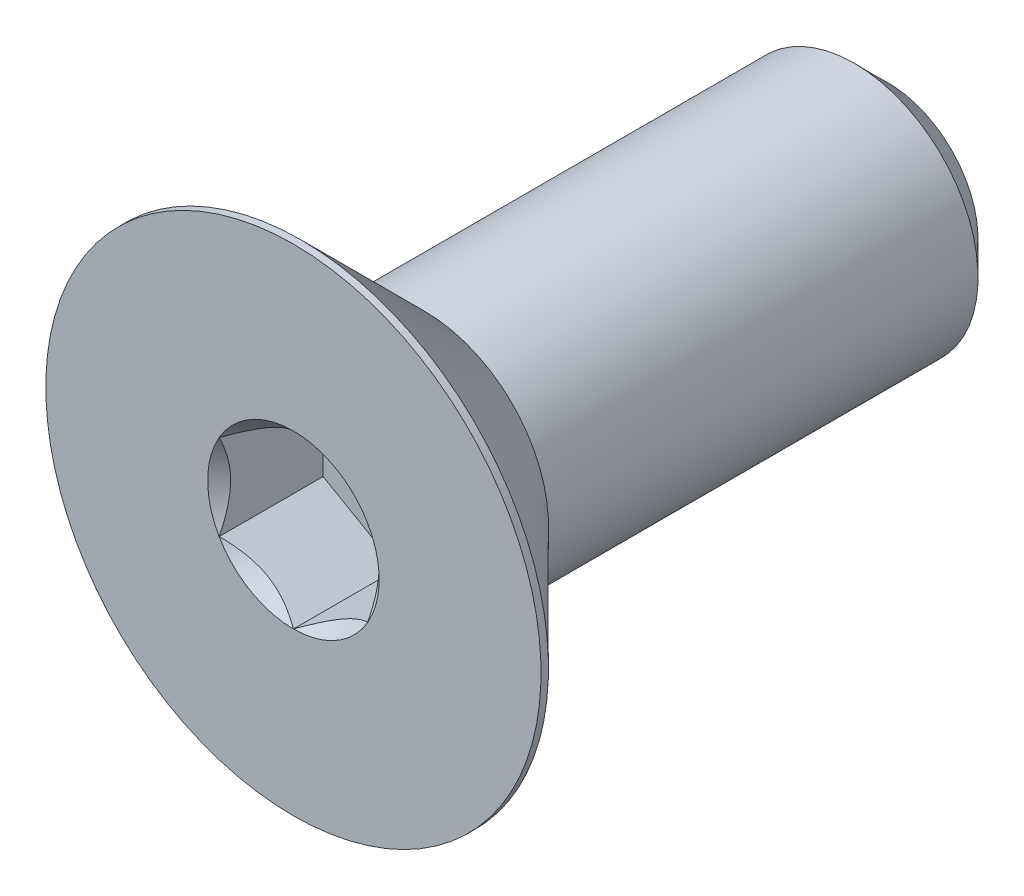
SolidWorks part; units mm, degrees
ref_plane "Front" through (0, 0, 0) normal (0, 0, 1) x (1, 0, 0)
ref_plane "Top" through (0, 0, 0) normal (0, 1, 0) x (1, 0, 0)
ref_plane "Right" through (0, 0, 0) normal (1, 0, 0) x (0, 0, -1)
sketch "Sketch11" plane through (0, 0, 0) normal (1, 0, 0) x (0, 0, -1)
  line L0 (-3, 2.5) -> (3, 2.5) construction
  line L5 (-3, 2.5) -> (-3, -2.5) construction
  line L6 (3, 1.25) -> (3, -1.25) construction
  line L7 (-2.99, 0.75) -> (-2.99, -0.75) construction
  line L8 (2.9719, 1.2987) -> (3.4219, 1.2987) construction
  line L9 (3.4219, 1.2987) -> (3.1969, 0.909) construction
  line L10 (3.1969, 0.909) -> (2.9719, 1.2987) construction
  line L11 (3.1688, 0.9577) -> (3.225, 0.9577) construction
  line L12 (3.1969, 0.9577) -> (3.1969, 0.909) construction
  line L13 (2.9859, 1.2744) -> (3.4078, 1.2744) construction
  line L14 (3.1969, 1.2987) -> (3.1969, 1.25) construction
  line L15 (3, 1.25) -> (3.3938, 1.25) construction
  line L17 (-2.925, 2.5) -> (-0.425, 0) construction
  line L18 (-0.425, 0) -> (-2.925, -2.5) construction
  point P3 (-1.5, 2.5)
  point P8 (0, 2.5)
  point P21 (3.1969, 1.2744)
  point P26 (-3, 0)
  point P28 (-2.99, 0)
  point P29 (3, 0)
  dimension "Length" = 6
  dimension "Head Diameter" = 5
  dimension "Thread Major Diameter" = 2.5
  dimension "Head Height" = 1.5
  dimension "Drive Size" = 1.5
  dimension "Thread Pitch" = 0.45
  dimension "D1" = 0.0563
  dimension "D2" = 0.01
  dimension "D3" = 0.075
  dimension "Countersink Angle" = 90
sketch "Sketch1" plane through (0, 0, 0) normal (1, 0, 0) x (0, 0, -1)
  line L2 (-1.5, 1.25) -> (3, 1.25)
  line L3 (3, 1.25) -> (3, 0)
  line L4 (-1.95, 1.25) -> (-1.95, 0)
  line L5 (-1.5, 1.25) -> (-1.95, 1.25)
  line L6 (-3, 2.5) -> (-3, -2.5) construction
  line L7 (3, 1.25) -> (3, -1.25) construction
  line L8 (-1.95, 0) -> (3, 0)
  dimension "D1" = 1.05
revolve "Revolve1" add sketch "Sketch1" angle 360 mid plane about L8
chamfer "Chamfer1" distance 0.3375 angle 45 1 edges at (0, -1.25, -3)
sketch "Sketch7" plane through (0, 0, 0) normal (1, 0, 0) x (0, 0, -1)
  line L2 (-3, 2.5) -> (-2.925, 2.5)
  line L5 (-1.5, 1.075) -> (-1.5, 0)
  line L6 (-3, 2.5) -> (-3, 0)
  line L8 (-3, 2.5) -> (-3, -2.5) construction
  line L9 (-3, 0) -> (-1.5, 0)
  line L12 (-2.925, 2.5) -> (-1.5, 1.075)
  line L13 (-2.925, 2.5) -> (-0.425, 0) construction
revolve "Revolve2" add sketch "Sketch7" angle 360 mid plane about L9 region at (0, 0.9623, 2.3521)
ref_plane "Plane1" through (0, 0, 1.5) normal (0, 0, 1) x (1, 0, 0)
sketch "Sketch5" plane through (0, 0, 3) normal (0, 0, 1) x (1, 0, 0)
  line L1 (0.75, -0.433) -> (0.75, 0.433)
  line L2 (0.75, 0.433) -> (0, 0.866)
  line L3 (0, 0.866) -> (-0.75, 0.433)
  line L4 (-0.75, 0.433) -> (-0.75, -0.433)
  line L5 (-0.75, -0.433) -> (0, -0.866)
  line L6 (0, -0.866) -> (0.75, -0.433)
  circle A0 centre (0, 0) radius 0.75 construction
extrude "Cut-Extrude2" cut sketch "Sketch5" against normal blind 1.05
sketch "Sketch6" plane through (0, 0, 3) normal (0, 0, -1) x (-1, 0, 0)
  circle A0 centre (0, 0) radius 0.866
extrude "Cut-Extrude3" cut sketch "Sketch6" along normal blind 1.05 draft 45
sketch "Sketch12" [suppressed] plane through (0, 0, -3) normal (0, 0, -1) x (-1, 0, 0)
  circle A0 centre (0, 0) radius 1.25 construction
  circle A1 centre (0, 0) radius 1.25
curve "Helix/Spiral1" [suppressed] pitch 0.45 height 6 turns 13.3333
sketch "Sketch13" [suppressed] plane through (0, 0, 0) normal (1, 0, 0) x (0, 0, -1)
  line L0 (2.9859, 1.2744) -> (3.4078, 1.2744)
  line L1 (3.4078, 1.2744) -> (3.225, 0.9577)
  line L2 (3.225, 0.9577) -> (3.1688, 0.9577)
  line L3 (3.1688, 0.9577) -> (2.9859, 1.2744)
sweep "Cut-Sweep1" [suppressed] cut profiles "Sketch13" path "Helix/Spiral1"
combine bodies "Combine1" [suppressed] operation type add bodies to combine 113 127
ref_axis "Axis1" through (0, 0, -3.3043) along (0, 0, 1)
equation "\"D1@Chamfer1\"=\"Thread Pitch@Sketch11\" * .75"
equation "\"D1@Cut-Extrude2\"= \"Head Height@Sketch11\" * .7"
equation "\"D1@Cut-Extrude3\" = \"D1@Cut-Extrude2\""
equation "\"D1@Sketch11\"=\"Thread Pitch@Sketch11\"/8"
equation "\"D3@Sketch11\"=\"Head Height@Sketch11\"*.05"
equation "\"D4@Helix/Spiral1\"=\"Thread Pitch@Sketch11\""
equation "\"D1@Sketch1\"=\"Head Height@Sketch11\"*.7"
equation "\"D3@Helix/Spiral1\"=\"Length@Sketch11\""
